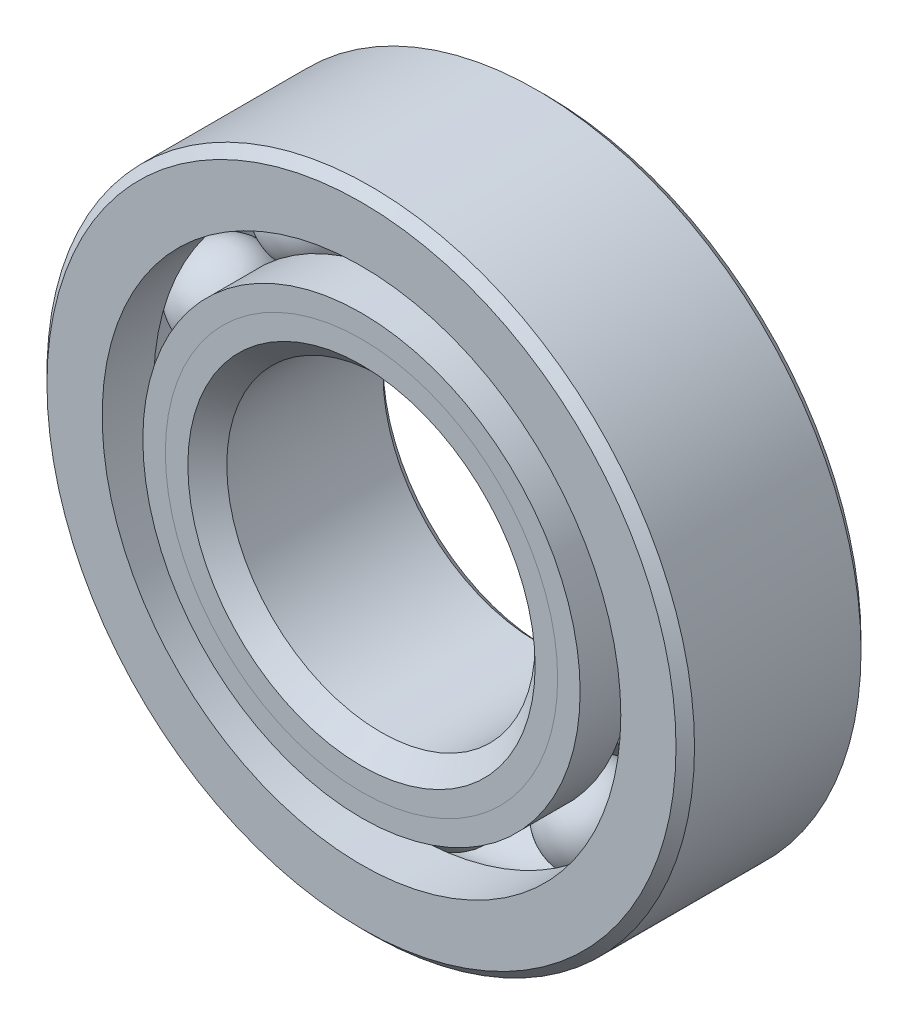
SolidWorks part; units mm, degrees
ref_plane "Front Plane" through (0, 0, 0) normal (0, 0, 1) x (1, 0, 0)
ref_plane "Top Plane" through (0, 0, 0) normal (0, 1, 0) x (1, 0, 0)
ref_plane "Right Plane" through (0, 0, 0) normal (1, 0, 0) x (0, 0, -1)
sketch "Sketch1" plane through (0, 0, 0) normal (1, 0, 0) x (0, 0, -1)
  line L0 (-6, 0) -> (6, 0) construction
  line L1 (0, 21) -> (0, -21) construction
  line L2 (5.4, 21) -> (-5.4, 21)
  line L3 (-5.4, 21) -> (-6, 20.4)
  line L4 (-6, 20.4) -> (-6, 16.8187)
  line L5 (-6, 16.8187) -> (-2.6667, 16.8187)
  line L6 (6, 16.8187) -> (2.6667, 16.8187)
  line L7 (6, 20.4) -> (6, 16.8187)
  line L8 (5.4, 21) -> (6, 20.4)
  line L9 (0, 21) -> (0, 15.5) construction
  line L10 (0, 15.5) -> (0, 10) construction
  arc A0 (-2.6667, 16.8187) -> (2.6667, 16.8187) centre (0, 15.5) cw
  point P14 (0, 10)
  dimension "Width" = 12
  dimension "OD" = 42
  dimension "D1" = 45
  dimension "D2" = 0.6
  dimension "D3" = 5.3333
  dimension "D4" = 1.3187
revolve "Revolve1" add sketch "Sketch1" angle 360 about L0
sketch "Sketch2" plane through (0, 0, 0) normal (1, 0, 0) x (0, 0, -1)
  line L0 (-6, 14.1813) -> (-2.6667, 14.1813)
  line L1 (-6, 20.4) -> (-6, -20.4) construction
  line L2 (-6, 14.1813) -> (-6, 12.7219)
  line L3 (-6, 12.7219) -> (-4.5406, 11.2625)
  line L4 (-4.5406, 11.2625) -> (0, 11.2625)
  line L5 (0, 21) -> (0, -21) construction
  line L6 (0, 11.2625) -> (0, 12.5251)
  line L7 (0, 12.5251) -> (0, 10) construction
  line L8 (-6, 14.1813) -> (-6, 11.2625) construction
  line L9 (-6, 11.2625) -> (-4.5406, 11.2625) construction
  arc A0 (-2.6667, 14.1813) -> (0, 12.5251) centre (0, 15.5) ccw
  arc A1 (2.6667, 16.8187) -> (-2.6667, 16.8187) centre (0, 15.5) ccw construction
  circle A2 centre (0, 15.5) radius 2.9749 construction
  dimension "D1" = 45
revolve "Revolve2" add sketch "Sketch2" angle 360 about L0
sketch "Sketch3" plane through (0, 0, 0) normal (1, 0, 0) x (0, 0, -1)
  line L0 (-6, 12.7219) -> (-4.5406, 11.2625)
  line L1 (-4.5406, 11.2625) -> (0, 11.2625)
  line L2 (0, 11.2625) -> (0, 12.5251)
  line L3 (-6, 12.7219) -> (-6, 11.2625)
  line L4 (-6, 14.1813) -> (-6, 11.2625) construction
  line L5 (-6, 11.2625) -> (-4.7375, 10)
  line L6 (-4.7375, 10) -> (5.4, 10)
  line L7 (5.4, 21) -> (5.4, -21) construction
  line L8 (5.4, 10) -> (6, 10.6)
  line L9 (6, -20.4) -> (6, 20.4) construction
  line L10 (6, 10.6) -> (6, 14.1813)
  line L11 (6, 14.1813) -> (2.6667, 14.1813)
  line L13 (5.4, 21) -> (6, 20.4) construction
  circle A0 centre (0, 15.5) radius 2.9749 construction
  arc A1 (2.6667, 14.1813) -> (0, 12.5251) centre (0, 15.5) cw
revolve "Revolve3" add sketch "Sketch3" angle 360 about L0
sketch "Sketch4" plane through (0, 0, 0) normal (1, 0, 0) x (0, 0, -1)
  line L0 (-2.9749, 15.5) -> (2.9749, 15.5)
  circle A1 centre (0, 15.5) radius 2.9749 construction
  arc A2 (-2.9749, 15.5) -> (2.9749, 15.5) centre (0, 15.5) cw
  arc A3 (2.6667, 16.8187) -> (-2.6667, 16.8187) centre (0, 15.5) ccw construction
revolve "Revolve4" add sketch "Sketch4" angle 360 about L0
ref_axis "Axis1" through (0, 0, -6) along (0, 0, 1)
pattern_circular "CirPattern1" count 10 every 36 about axis through (0, 0, -6) along (0, 0, 1) of bodies 104
equation "\"D2@Sketch1\" = \"Width@Sketch1\"*.05"
equation "\"D3@Sketch1\" = \"Width@Sketch1\"/2.25"
equation "\"D4@Sketch1\" = (((\"OD@Sketch1\"-\"Width@Sketch1\")/2)/3.25)/3.5"
equation "\"D2@CirPattern1\" = 360/\"Balls@CirPattern1\""
